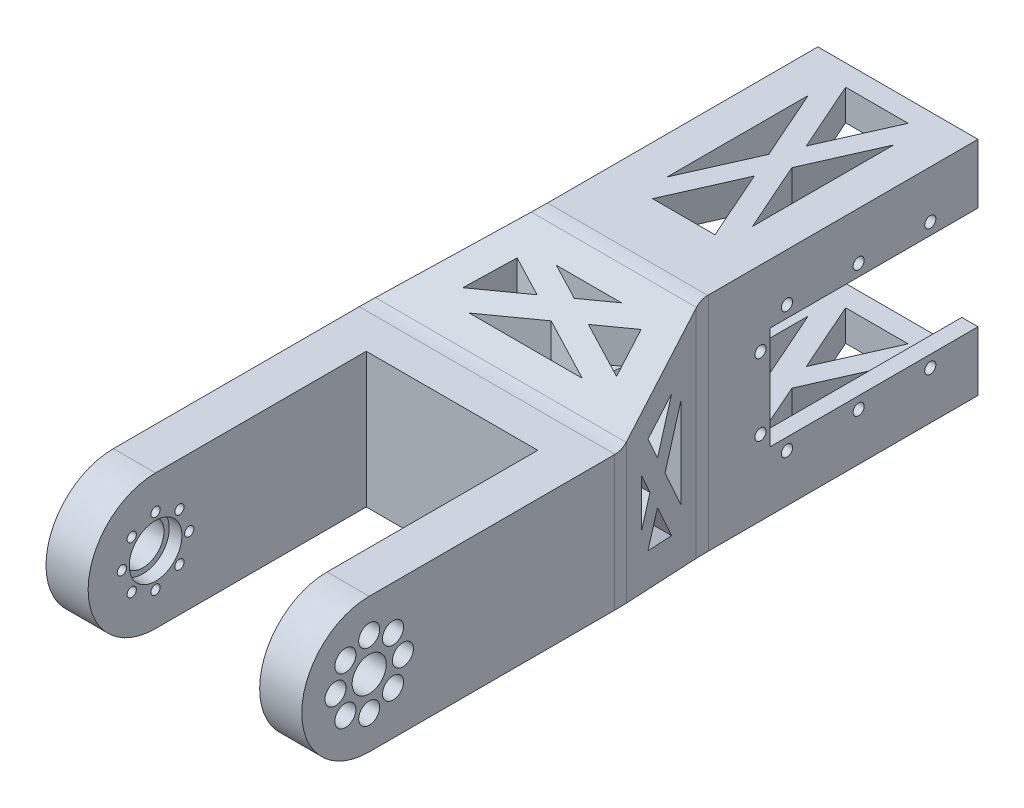
SolidWorks part; units mm, degrees
ref_plane "Front Plane" through (0, 0, 0) normal (0, 0, 1) x (1, 0, 0)
ref_plane "Top Plane" through (0, 0, 0) normal (0, 1, 0) x (1, 0, 0)
ref_plane "Right Plane" through (0, 0, 0) normal (1, 0, 0) x (0, 0, -1)
sketch "Sketch1" plane through (0, 0, 0) normal (1, 0, 0) x (0, 0, -1)
  line L0 (0, 0) -> (140, 0) construction
  line L1 (70, 0) -> (70, 48.1437) construction
  line L2 (50, 0) -> (50, 26.325) construction
  line L4 (50, 26.325) -> (106.5, 26.325)
  line L5 (50, 26.325) -> (50, -26.325) construction
  line L6 (50, -26.325) -> (106.5, -26.325)
  line L7 (106.5, 12.2) -> (106.5, -12.2)
  line L9 (21.2298, 12.2) -> (97.1013, 12.2) construction
  line L11 (125, 12.2) -> (155.825, 12.2)
  line L12 (125, -12.2) -> (155.825, -12.2)
  line L14 (106.5, -12.2) -> (106.5, -26.325) construction
  line L15 (106.5, 26.325) -> (106.5, 12.2) construction
  line L16 (125, 72.2052) -> (125, -87.6659) construction
  line L20 (106.5, 12.2) -> (125, 12.2)
  line L21 (50, 26.325) -> (50, -26.325)
  line L25 (106.5, -12.2) -> (125, -12.2)
  line L26 (100, 26.325) -> (100, -26.325)
  line L27 (106.5, 26.325) -> (155.825, 26.325)
  line L28 (155.825, 26.325) -> (155.825, 12.2)
  line L29 (155.825, -26.325) -> (155.825, -12.2)
  line L30 (106.5, -26.325) -> (155.825, -26.325)
  line L31 (0, 16) -> (50, 16)
  line L32 (0, -16) -> (50, -16)
  circle A0 centre (0, 0) radius 11 construction
  circle A1 centre (0, 0) radius 4 construction
  circle A2 centre (-8, 0) radius 1.1
  circle A3 centre (-5.6569, 5.6569) radius 1.1
  circle A4 centre (0, 8) radius 1.1
  circle A5 centre (5.6569, 5.6569) radius 1.1
  circle A6 centre (8, 0) radius 1.1
  circle A7 centre (5.6569, -5.6569) radius 1.1
  circle A8 centre (0, -8) radius 1.1
  circle A9 centre (-5.6569, -5.6569) radius 1.1
  circle A10 centre (145.6569, -5.6569) radius 1.1 construction
  circle A11 centre (140, -8) radius 1.1 construction
  circle A12 centre (134.3431, -5.6569) radius 1.1 construction
  circle A13 centre (132, 0) radius 1.1 construction
  circle A14 centre (134.3431, 5.6569) radius 1.1 construction
  circle A15 centre (140, 8) radius 1.1 construction
  circle A16 centre (145.6569, 5.6569) radius 1.1 construction
  circle A17 centre (148, 0) radius 1.1 construction
  circle A18 centre (140, 0) radius 4 construction
  circle A19 centre (140, 0) radius 11 construction
  circle A20 centre (127.5, 15) radius 1.325
  circle A21 centre (144.5, 15) radius 1.325
  circle A22 centre (144.5, -15) radius 1.325
  circle A23 centre (127.5, -15) radius 1.325
  arc A24 (0, 16) -> (0, -16) centre (0, 0) ccw
  arc A25 (0, -16) -> (16, 0) centre (0, 0) ccw construction
  arc A26 (16, 0) -> (0, 16) centre (0, 0) ccw construction
  circle A27 centre (0, 0) radius 16 construction
  circle A30 centre (150.825, 15) radius 5 construction
  circle A31 centre (144.5, 21.325) radius 5 construction
  circle A32 centre (144.5, -21.325) radius 5 construction
  circle A33 centre (150.825, -15) radius 5 construction
  circle A40 centre (0, 0) radius 4.05
  circle A41 centre (110.5, 15) radius 1.325
  circle A42 centre (104.2, 8.5) radius 1.325
  circle A43 centre (110.5, -15) radius 1.325
  circle A44 centre (104.2, -8.5) radius 1.325
  point P23 (0, 0)
  point P42 (140, 0)
  point P54 (144.5, 15)
  point P59 (50, 0)
  point P63 (16, 0)
  point P72 (160.525, 15)
  dimension "D2" = 8
  dimension "D3" = 22
  dimension "D4" = 2.2
  dimension "D9" = 2.65
  dimension "D19" = 17
  dimension "D15" = 8.1
  dimension "D20" = 6.3
  dimension "D13" = 10
  dimension "D1" = 140
  dimension "D5" = 8
  dimension "D7" = 15
  dimension "D8" = 12.5
  dimension "D10" = 4.5
  dimension "D11" = 50
  dimension "D14" = 2.8
  dimension "D16" = 33.5
  dimension "D17" = 15
  dimension "D21" = 6.5
  dimension "D22" = 40
  dimension "D12" = 5
  dimension "D6" = 8
extrude "Boss-Extrude1" add sketch "Sketch1" against normal blind 10 from offset 20.35 contours A24 L21 A40 A2 A3 A4 A5 A6 A7 A8 A9 region at (0, 0, -19.4093) offset against normal yes
extrude "Boss-Extrude2" add sketch "Sketch1<8>" along normal blind 10 from offset 20.35 separate body contours A24 L21 A40 A2 A3 A4 A5 A6 A7 A8 A9 region at (0, 0, -19.4093)
sketch "Sketch1<8>" plane through (0, 0, 0) normal (1, 0, 0) x (0, 0, -1) same geometry as "Sketch1"
extrude "Boss-Extrude3" add sketch "Sketch1<9>" against normal blind 3.85 from offset 15.15 separate body contours L12 L25 L7 L20 L11 L28 L27 L4 L26 L6 A43 A42 A41 A22 A21 A20 A23 A44 region at (0, 25.5576, -103.25) offset against normal yes
sketch "Sketch1<9>" plane through (0, 0, 0) normal (1, 0, 0) x (0, 0, -1) same geometry as "Sketch1"
extrude "Boss-Extrude4" add sketch "Sketch1<10>" along normal blind 3.85 from offset 15.15 separate body contours L12 L25 L7 L20 L11 L28 L27 L4 L26 L6 A43 A42 A41 A22 A21 A20 A23 A44 region at (0, 25.5576, -103.25)
sketch "Sketch1<10>" plane through (0, 0, 0) normal (1, 0, 0) x (0, 0, -1) same geometry as "Sketch1"
sketch "Sketch3" plane through (0, 0, -50) normal (0, 0, -1) x (-1, 0, 0)
  line L1 (-30.35, 16) -> (30.35, 16)
  line L2 (-30.35, 16) -> (-30.35, -16)
  line L3 (-30.35, -16) -> (30.35, -16)
  line L4 (30.35, 16) -> (30.35, -16)
  line L5 (-30.35, 16) -> (30.35, -16) construction
  line L6 (-30.35, -16) -> (30.35, 16) construction
  point P4 (0, 0)
extrude "Boss-Extrude6" add sketch "Sketch3" along normal blind 10
sketch "Sketch4" plane through (0, 0, -100) normal (0, 0, 1) x (1, 0, 0)
  line L1 (-19, 26.325) -> (19, 26.325)
  line L2 (-19, 26.325) -> (-19, -26.325)
  line L3 (-19, -26.325) -> (19, -26.325)
  line L4 (19, 26.325) -> (19, -26.325)
  line L5 (-19, 26.325) -> (19, -26.325) construction
  line L6 (-19, -26.325) -> (19, 26.325) construction
  point P4 (0, 0)
extrude "Boss-Extrude7" add sketch "Sketch4" along normal blind 10
loft "Loft2" add section face at (0, 0, -60) section face at (0, 0, -90) connector at (-30.35, 16, -60) connector at (-19, 26.325, -90)
ref_axis "Axis1" through (19, 15, -144.5) along (-1, 0, 0)
ref_axis "Axis2" through (-19, 15, -110.5) along (1, 0, 0)
ref_plane "Plane4" through (0, 15, 0) normal (0, 1, 0) x (1, 0, 0)
ref_plane "Plane5" through (0, 19, 0) normal (0, 1, 0) x (1, 0, 0)
sketch "Sketch5" plane through (0, 26.325, 0) normal (0, 1, 0) x (1, 0, 0)
  line L1 (-15.15, 100) -> (15.15, 100)
  line L2 (-15.15, 100) -> (-15.15, 155.825)
  line L3 (-15.15, 155.825) -> (15.15, 155.825)
  line L4 (15.15, 100) -> (15.15, 155.825)
  line L5 (-15.15, 100) -> (15.15, 155.825) construction
  line L6 (-15.15, 155.825) -> (15.15, 100) construction
  point P4 (0, 127.9125)
extrude "Boss-Extrude8" add sketch "Sketch5" against normal up to surface (7.325 mm away) up to plane "Plane5"
ref_axis "Axis3" through (19, -15, -110.5) along (-1, 0, 0)
ref_axis "Axis4" through (-19, -15, -144.5) along (1, 0, 0)
ref_plane "Plane7" through (0, -15, 0) normal (0, -1, 0) x (-1, 0, 0)
ref_plane "Plane8" through (0, -19, 0) normal (0, -1, 0) x (-1, 0, 0)
extrude "Boss-Extrude9" add sketch "Sketch5<2>" against normal up to surface (52.65 mm away) from surface up to face at (-2.375, -26.325, -117.1844) starting at plane "Plane8"
sketch "Sketch5<2>" plane through (0, 26.325, 0) normal (0, 1, 0) x (1, 0, 0) same geometry as "Sketch5"
sketch "Sketch6" plane through (0, -19, 0) normal (0, 1, 0) x (1, 0, 0)
  line L0 (10.15, 144.6526) -> (12.4358, 149.8124) construction
  line L1 (-12.4358, 106.0126) -> (-10.15, 111.1724) construction
  line L2 (-12.4358, 106.0126) -> (7.8642, 151.8376) construction
  line L3 (-7.8642, 103.9874) -> (-7.4157, 105) construction
  line L4 (15.15, 100) -> (15.15, 155.825)
  line L5 (15.15, 155.825) -> (-15.15, 155.825)
  line L6 (-15.15, 155.825) -> (-15.15, 100)
  line L7 (-15.15, 100) -> (15.15, 100)
  line L8 (15.15, 100) -> (15.15, 155.825)
  line L9 (15.15, 155.825) -> (-15.15, 155.825)
  line L10 (-15.15, 155.825) -> (-15.15, 100)
  line L11 (-15.15, 100) -> (15.15, 100)
  line L12 (0, 127.9125) -> (-1.3672, 130.9987) construction
  line L13 (-1.3672, 124.8263) -> (0, 127.9125) construction
  line L14 (10.15, 111.1724) -> (2.7343, 127.9125)
  line L15 (7.4157, 105) -> (0, 121.7401)
  line L16 (10.15, 105) -> (10.15, 150.825)
  line L17 (10.15, 150.825) -> (-10.15, 150.825)
  line L18 (-10.15, 150.825) -> (-10.15, 105)
  line L19 (-10.15, 105) -> (10.15, 105)
  line L20 (10.15, 111.1724) -> (10.15, 144.6526)
  line L21 (7.4157, 150.825) -> (-7.4157, 150.825)
  line L22 (-10.15, 144.6526) -> (-10.15, 111.1724)
  line L23 (-7.4157, 105) -> (7.4157, 105)
  line L24 (-7.4157, 105) -> (0, 121.7401)
  line L25 (-10.15, 111.1724) -> (-2.7343, 127.9125)
  line L26 (-7.8642, 103.9874) -> (12.4358, 149.8124) construction
  line L27 (7.4157, 150.825) -> (7.8642, 151.8376) construction
  line L28 (12.4358, 106.0126) -> (10.15, 111.1724) construction
  line L29 (-7.4157, 150.825) -> (-7.8642, 151.8376) construction
  line L30 (12.4358, 106.0126) -> (-7.8642, 151.8376) construction
  line L31 (-10.15, 144.6526) -> (-12.4358, 149.8124) construction
  line L32 (7.8642, 103.9874) -> (-12.4358, 149.8124) construction
  line L33 (7.8642, 103.9874) -> (7.4157, 105) construction
  line L34 (10.15, 105) -> (10.15, 111.1724) construction
  line L35 (10.15, 105) -> (1.3672, 124.8263) construction
  line L36 (10.15, 105) -> (-10.15, 150.825) construction
  line L37 (7.4157, 105) -> (10.15, 105) construction
  line L38 (-10.15, 111.1724) -> (-10.15, 105) construction
  line L39 (-10.15, 105) -> (-1.3672, 124.8263) construction
  line L40 (-10.15, 105) -> (10.15, 150.825) construction
  line L41 (-10.15, 105) -> (-7.4157, 105) construction
  line L42 (-10.15, 150.825) -> (-10.15, 144.6526) construction
  line L43 (-7.4157, 150.825) -> (-10.15, 150.825) construction
  line L44 (-1.3672, 130.9987) -> (-10.15, 150.825) construction
  line L45 (1.3672, 130.9987) -> (10.15, 150.825) construction
  line L46 (10.15, 150.825) -> (7.4157, 150.825) construction
  line L47 (10.15, 144.6526) -> (10.15, 150.825) construction
  line L48 (0, 134.0849) -> (-7.4157, 150.825)
  line L49 (2.7343, 127.9125) -> (1.3672, 130.9987) construction
  line L50 (1.3672, 130.9987) -> (0, 134.0849) construction
  line L51 (0, 134.0849) -> (7.4157, 150.825)
  line L52 (-1.3672, 130.9987) -> (0, 134.0849) construction
  line L53 (-2.7343, 127.9125) -> (-1.3672, 130.9987) construction
  line L54 (-2.7343, 127.9125) -> (-10.15, 144.6526)
  line L55 (-1.3672, 124.8263) -> (-2.7343, 127.9125) construction
  line L56 (0, 121.7401) -> (-1.3672, 124.8263) construction
  line L57 (2.7343, 127.9125) -> (10.15, 144.6526)
  line L58 (0, 121.7401) -> (1.3672, 124.8263) construction
  line L59 (1.3672, 124.8263) -> (2.7343, 127.9125) construction
  line L60 (1.3672, 124.8263) -> (0, 127.9125) construction
  line L61 (0, 127.9125) -> (1.3672, 130.9987) construction
  arc A0 (12.4358, 106.0126) -> (7.8642, 103.9874) centre (10.15, 105) cw construction
  arc A1 (-7.8642, 151.8376) -> (-12.4358, 149.8124) centre (-10.15, 150.825) ccw construction
  arc A2 (-7.8642, 103.9874) -> (-12.4358, 106.0126) centre (-10.15, 105) cw construction
  arc A3 (12.4358, 149.8124) -> (7.8642, 151.8376) centre (10.15, 150.825) ccw construction
  dimension "D3" = 2.5
  dimension "D1" = 0
  dimension "D2" = 5
  dimension "D4" = 2.5
  dimension "D5" = 2.5
  dimension "D6" = 2.5
extrude "Cut-Extrude1" cut sketch "Sketch6" against normal through all both and the other way through all contours L24 L23 L15 | L57 L14 L20 | L48 L51 L21 | L25 L54 L22 region at (7.6781, -19, -127.9125) region at (0, -19, -110.58) region at (0, -19, -145.245) region at (-7.6781, -19, -127.9125)
sketch "Sketch8" plane through (0, 0, 0) normal (1, 0, 0) x (0, 0, -1)
  line L0 (78.9297, 14.5832) -> (69.9046, 11.4771)
  line L1 (67.5, 5.5799) -> (67.5, -5.5799)
  line L2 (69.9046, -11.4771) -> (78.9297, -14.5832)
  line L3 (82.5, -10.7424) -> (82.5, 10.7424)
  line L4 (90, 26.325) -> (60, 16)
  line L5 (90, -26.325) -> (90, 26.325)
  line L6 (60, -16) -> (90, -26.325)
  line L7 (60, 16) -> (60, -16)
  line L8 (90, 26.325) -> (60, 16)
  line L9 (90, -26.325) -> (90, 26.325)
  line L10 (60, -16) -> (90, -26.325)
  line L11 (60, 16) -> (60, -16)
  line L12 (67.5, -10.6495) -> (82.5, 15.812) construction
  line L13 (67.5, 10.6495) -> (82.5, -15.812) construction
  line L14 (67.5, 5.5799) -> (70.6631, 0)
  line L15 (69.9046, -11.4771) -> (73.5368, -5.0695)
  line L16 (69.9046, 11.4771) -> (73.5368, 5.0695)
  line L17 (67.5, -5.5799) -> (70.6631, 0)
  line L18 (78.9297, -14.5832) -> (80.3251, -17.0448) construction
  line L19 (65.3251, 9.4166) -> (67.5, 5.5799) construction
  line L20 (65.3251, 9.4166) -> (80.3251, -17.0448) construction
  line L21 (69.6749, 11.8823) -> (69.9046, 11.4771) construction
  line L22 (69.6749, 11.8823) -> (84.6749, -14.5791) construction
  line L23 (65.3251, -9.4166) -> (67.5, -5.5799) construction
  line L24 (65.3251, -9.4166) -> (80.3251, 17.0448) construction
  line L25 (69.6749, -11.8823) -> (69.9046, -11.4771) construction
  line L26 (69.6749, -11.8823) -> (84.6749, 14.5791) construction
  line L27 (82.5, -10.7424) -> (84.6749, -14.5791) construction
  line L28 (82.5, 10.7424) -> (84.6749, 14.5791) construction
  line L29 (78.9297, 14.5832) -> (80.3251, 17.0448) construction
  line L30 (76.4105, 0) -> (82.5, -10.7424)
  line L31 (74.9737, 2.5348) -> (76.4105, 0) construction
  line L32 (73.5368, 5.0695) -> (74.9737, 2.5348) construction
  line L33 (73.5368, 5.0695) -> (78.9297, 14.5832)
  line L34 (72.0999, 2.5348) -> (73.5368, 5.0695) construction
  line L35 (70.6631, 0) -> (72.0999, 2.5348) construction
  line L36 (73.5368, -5.0695) -> (78.9297, -14.5832)
  line L37 (70.6631, 0) -> (72.0999, -2.5348) construction
  line L38 (72.0999, -2.5348) -> (73.5368, -5.0695) construction
  line L39 (76.4105, 0) -> (82.5, 10.7424)
  line L40 (73.5368, -5.0695) -> (74.9737, -2.5348) construction
  line L41 (74.9737, -2.5348) -> (76.4105, 0) construction
  line L42 (67.5, 10.6495) -> (67.5, 5.5799) construction
  line L43 (67.5, -10.6495) -> (69.9046, -11.4771) construction
  line L44 (67.5, -10.6495) -> (82.5, -15.812) construction
  line L45 (67.5, -5.5799) -> (67.5, -10.6495) construction
  line L46 (67.5, 10.6495) -> (67.5, -10.6495) construction
  line L47 (82.5, 15.812) -> (78.9297, 14.5832) construction
  line L48 (69.9046, 11.4771) -> (67.5, 10.6495) construction
  line L49 (82.5, 15.812) -> (67.5, 10.6495) construction
  line L50 (82.5, -15.812) -> (82.5, -10.7424) construction
  line L51 (82.5, 10.7424) -> (82.5, 15.812) construction
  line L52 (82.5, -15.812) -> (82.5, 15.812) construction
  line L53 (78.9297, -14.5832) -> (82.5, -15.812) construction
  arc A0 (65.3251, 9.4166) -> (69.6749, 11.8823) centre (67.5, 10.6495) cw construction
  arc A1 (80.3251, -17.0448) -> (84.6749, -14.5791) centre (82.5, -15.812) ccw construction
  arc A2 (69.6749, -11.8823) -> (65.3251, -9.4166) centre (67.5, -10.6495) cw construction
  arc A3 (84.6749, 14.5791) -> (80.3251, 17.0448) centre (82.5, 15.812) ccw construction
  dimension "D3" = 2.5
  dimension "D1" = 0
  dimension "D2" = 7.5
  dimension "D4" = 2.5
extrude "Cut-Extrude2" cut sketch "Sketch8" against normal through all both and the other way through all contours L36 L15 L2 | L1 L17 L14 | L16 L33 L0 | L39 L30 L3 region at (0, 10.3766, -74.1237) region at (0, 0, -68.5544) region at (0, -10.3766, -74.1237) region at (0, 0, -80.4702)
sketch "Sketch9" plane through (0, 0, 0) normal (0, 1, 0) x (1, 0, 0)
  line L0 (-14.705, 80.1573) -> (-18.2434, 70.8047)
  line L1 (-13.4047, 67.5) -> (13.4047, 67.5)
  line L2 (18.2434, 70.8047) -> (14.705, 80.1573)
  line L3 (7.7297, 82.5) -> (-7.7297, 82.5)
  line L4 (-19, 90) -> (-30.35, 60)
  line L5 (19, 90) -> (-19, 90)
  line L6 (30.35, 60) -> (19, 90)
  line L7 (-30.35, 60) -> (30.35, 60)
  line L8 (-19, 90) -> (-30.35, 60)
  line L9 (19, 90) -> (-19, 90)
  line L10 (30.35, 60) -> (19, 90)
  line L11 (-30.35, 60) -> (30.35, 60)
  line L12 (-13.8187, 82.5) -> (19.4937, 67.5) construction
  line L13 (-19.4937, 67.5) -> (13.8187, 82.5) construction
  line L14 (-18.2434, 70.8047) -> (-6.089, 76.2777)
  line L15 (-7.7297, 82.5) -> (0, 79.0194)
  line L16 (-13.4047, 67.5) -> (0, 73.5359)
  line L17 (-14.705, 80.1573) -> (-6.089, 76.2777)
  line L18 (18.2434, 70.8047) -> (20.5201, 69.7796) construction
  line L19 (-12.7922, 84.7796) -> (-7.7297, 82.5) construction
  line L20 (-12.7922, 84.7796) -> (20.5201, 69.7796) construction
  line L21 (-14.8451, 80.2204) -> (-14.705, 80.1573) construction
  line L22 (-14.8451, 80.2204) -> (18.4672, 65.2204) construction
  line L23 (14.705, 80.1573) -> (14.8451, 80.2204) construction
  line L24 (-18.4672, 65.2204) -> (14.8451, 80.2204) construction
  line L25 (7.7297, 82.5) -> (12.7922, 84.7796) construction
  line L26 (-20.5201, 69.7796) -> (12.7922, 84.7796) construction
  line L27 (13.4047, 67.5) -> (18.4672, 65.2204) construction
  line L28 (-18.4672, 65.2204) -> (-13.4047, 67.5) construction
  line L29 (-20.5201, 69.7796) -> (-18.2434, 70.8047) construction
  line L30 (13.8187, 82.5) -> (7.7297, 82.5) construction
  line L31 (-7.7297, 82.5) -> (-13.8187, 82.5) construction
  line L32 (13.8187, 82.5) -> (-13.8187, 82.5) construction
  line L33 (-13.8187, 82.5) -> (-14.705, 80.1573) construction
  line L34 (-13.8187, 82.5) -> (-19.4937, 67.5) construction
  line L35 (-18.2434, 70.8047) -> (-19.4937, 67.5) construction
  line L36 (14.705, 80.1573) -> (13.8187, 82.5) construction
  line L37 (19.4937, 67.5) -> (13.8187, 82.5) construction
  line L38 (13.4047, 67.5) -> (19.4937, 67.5) construction
  line L39 (-19.4937, 67.5) -> (-13.4047, 67.5) construction
  line L40 (-19.4937, 67.5) -> (19.4937, 67.5) construction
  line L41 (19.4937, 67.5) -> (18.2434, 70.8047) construction
  line L42 (6.089, 76.2777) -> (14.705, 80.1573)
  line L43 (0, 73.5359) -> (3.0445, 74.9068) construction
  line L44 (3.0445, 74.9068) -> (6.089, 76.2777) construction
  line L45 (6.089, 76.2777) -> (18.2434, 70.8047)
  line L46 (3.0445, 77.6486) -> (6.089, 76.2777) construction
  line L47 (0, 79.0194) -> (3.0445, 77.6486) construction
  line L48 (0, 79.0194) -> (7.7297, 82.5)
  line L49 (-3.0445, 77.6486) -> (0, 79.0194) construction
  line L50 (-6.089, 76.2777) -> (-3.0445, 77.6486) construction
  line L51 (0, 73.5359) -> (13.4047, 67.5)
  line L52 (-6.089, 76.2777) -> (-3.0445, 74.9068) construction
  line L53 (-3.0445, 74.9068) -> (0, 73.5359) construction
  arc A0 (-20.5201, 69.7796) -> (-18.4672, 65.2204) centre (-19.4937, 67.5) ccw construction
  arc A1 (12.7922, 84.7796) -> (14.8451, 80.2204) centre (13.8187, 82.5) cw construction
  arc A2 (-12.7922, 84.7796) -> (-14.8451, 80.2204) centre (-13.8187, 82.5) ccw construction
  arc A3 (20.5201, 69.7796) -> (18.4672, 65.2204) centre (19.4937, 67.5) cw construction
  dimension "D3" = 2.5
  dimension "D1" = 0
  dimension "D2" = 7.5
  dimension "D4" = 2.5
extrude "Cut-Extrude3" cut sketch "Sketch9" against normal through all both and the other way through all contours L17 L0 L14 | L15 L48 L3 | L42 L45 L2 | L51 L16 L1 region at (-13.0124, 0, -75.7466) region at (0, 0, -69.512) region at (13.0124, 0, -75.7466) region at (0, 0, -81.3398)
fillet "Fillet1" radius 10 8 edges at (0, -16, -60) (30.35, 0, -60) (0, 16, -60) (-30.35, 0, -60)
sketch "Sketch10" plane through (30.35, 0, 0) normal (1, 0, 0) x (0, 0, -1)
  circle A0 centre (0, 8) radius 2.5
  dimension "D1" = 5
extrude "Cut-Extrude4" cut sketch "Sketch10" against normal offset from surface (6 mm away) 4 up to face at (20.35, 0, -4.05)
pattern_circular "CirPattern1" count 8 over 360 about axis through (30.35, 0, 0) along (-1, 0, 0) of "Cut-Extrude4" reverse direction yes
mirror "Mirror1" about plane through (0, 0, 0) normal (1, 0, 0) of "Cut-Extrude4", "CirPattern1"
sketch "Sketch11" plane through (-20.35, 0, 0) normal (1, 0, 0) x (0, 0, -1)
  circle A0 centre (0, 0) radius 6.25
  dimension "D1" = 12.5
extrude "Cut-Extrude5" cut sketch "Sketch11" against normal blind 3
sketch "Sketch12" plane through (-30.35, 0, 0) normal (-1, 0, 0) x (0, 0, 1)
  circle A0 centre (0, 0) radius 5
  dimension "D1" = 10
extrude "Cut-Extrude6" cut sketch "Sketch12" against normal blind 10
